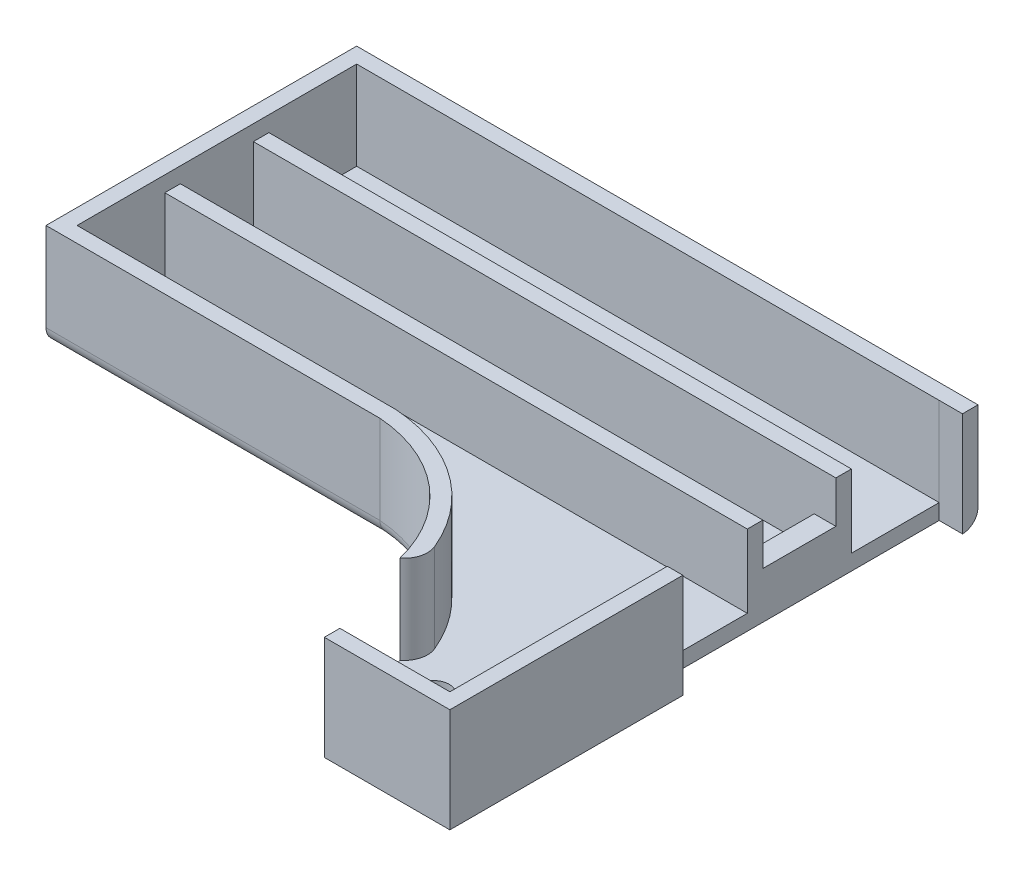
SolidWorks part; units mm, degrees
ref_plane "Alzado" through (0, 0, 0) normal (0, 0, 1) x (1, 0, 0)
ref_plane "Planta" through (0, 0, 0) normal (0, 1, 0) x (1, 0, 0)
ref_plane "Vista lateral" through (0, 0, 0) normal (1, 0, 0) x (0, 0, -1)
sketch "Croquis1" plane through (0, 0, 0) normal (0, 1, 0) x (1, 0, 0)
  line L0 (20, -10) -> (20, -24)
  line L1 (20, -24) -> (9, -24)
  line L2 (-20, -10) -> (-20, 10)
  line L3 (-20, 10) -> (20, 10)
  line L4 (20, -10) -> (20, 10)
  line L5 (-20, -10) -> (1.5, -10)
  arc A0 (9, -24) -> (1.5, -10) centre (0.7933, -19.3875) ccw
  point P0 (0, 0)
  point P10 (1.5, -10)
  dimension "D1" = 20
  dimension "D2" = 40
  dimension "D3" = 14
  dimension "D4" = 11
  dimension "D5" = 21.5
extrude "Saliente-Extruir2" add sketch "Croquis1" along normal blind 4 contours L4 L3 L2 L5 A0 L1 L0
shell "Vaciado1" thickness 1 removed face at (2.3903, 4, 7.657)
sketch "Croquis9" plane through (20, 0, 0) normal (1, 0, 0) x (0, 0, -1)
  line L0 (0, 4) -> (0, 0)
  line L1 (10, 4) -> (-24, 4) construction
  line L2 (-24, 0) -> (10, 0) construction
  line L3 (10, 4) -> (10, 0) construction
  line L5 (-9.0006, 0) -> (9.0006, 0)
  line L6 (-9.0006, 0) -> (-9.0006, 4)
  line L7 (-9.0006, 4) -> (9.0006, 4)
  line L8 (9.0006, 0) -> (9.0006, 4)
  line L9 (-9.0006, 0) -> (9.0006, 4) construction
  line L10 (-9.0006, 4) -> (9.0006, 0) construction
  point P8 (0, 2)
  line M2 (-24, 0) -> (10, 0)
  line M4 (10, 4) -> (-24, 4)
  dimension "D1" = 10
extrude "Cortar-Extruir2" cut sketch "Croquis9" against normal blind 1.5 contours L8 L0 M2 M4 | L6 L0 M2 M4 region at (20, 2, -4.5003) region at (20, 2, 4.5003)
sketch "Croquis12" plane through (0, 1, 0) normal (0, 1, 0) x (1, 0, 0)
  line L0 (18.5, -0.0003) -> (-19, 0) construction
  line L1 (18.5, -9.0006) -> (18.5, 9) construction
  line L2 (-19, -9) -> (-19, 9) construction
  line L3 (-0.25, -2.8502) -> (-0.25, 2.8498)
  line L5 (18.5, -2.3502) -> (-19, -2.3502)
  line L6 (18.5, -2.3502) -> (18.5, -3.3502)
  line L7 (18.5, -3.3502) -> (-19, -3.3502)
  line L8 (-19, -2.3502) -> (-19, -3.3502)
  line L9 (18.5, -2.3502) -> (-19, -3.3502) construction
  line L10 (18.5, -3.3502) -> (-19, -2.3502) construction
  line L11 (18.5, 2.3498) -> (-19, 2.3498)
  line L12 (18.5, 2.3498) -> (18.5, 3.3498)
  line L13 (18.5, 3.3498) -> (-19, 3.3498)
  line L14 (-19, 2.3498) -> (-19, 3.3498)
  line L15 (18.5, 2.3498) -> (-19, 3.3498) construction
  line L16 (18.5, 3.3498) -> (-19, 2.3498) construction
  point P9 (-0.25, -0.0002)
  dimension "D1" = 5.7
  dimension "D2" = 1
  dimension "D3" = 1
extrude "Saliente-Extruir6" add sketch "Croquis12" along normal blind 4.7 contours L7 L8 L5 L6 | L13 L14 L11 L12
sketch "Croquis14" plane through (0, 1, 0) normal (0, 1, 0) x (1, 0, 0)
  line L0 (18.5, 2.3498) -> (-19, 2.3498) construction
  line L1 (18.5, -2.3502) -> (17.1045, -2.3502)
  line L2 (18.5, -2.3502) -> (18.5, 2.3498)
  line L3 (18.5, 2.3498) -> (17.1045, 2.3498)
  line L4 (17.1045, -2.3502) -> (17.1045, 2.3498)
extrude "Saliente-Extruir7" add sketch "Croquis14" along normal blind 2
sketch "Croquis15" plane through (0, 1, 0) normal (0, 1, 0) x (1, 0, 0)
  line L0 (18.5, -3.3502) -> (-19, -3.3502) construction
  circle A0 centre (14.5685, -11.6502) radius 0.8
  dimension "D1" = 1.6
  dimension "D2" = 8.3
extrude "Saliente-Extruir8" add sketch "Croquis15" along normal blind 3.5
sketch "Croquis16" plane through (0, 4, 0) normal (0, 1, 0) x (1, 0, 0)
  line L0 (14.8572, -23) -> (14.8572, -17.9) construction
  line L1 (14.8572, -17.9) -> (12.8572, -17.9) construction
  line L2 (19, -23) -> (10.5607, -23) construction
  circle A0 centre (12.8572, -17.9) radius 0.8
  dimension "D3" = 1.6
  dimension "D1" = 5.1
  dimension "D2" = 2
extrude "Saliente-Extruir11" add sketch "Croquis16" along normal blind 1.78 and the other way up to vertex (3 mm away) other way up to point (18.5, 1, 9.0006)
sketch "Croquis59" plane through (0, 0, 24) normal (0, 0, 1) x (1, 0, 0)
  line L0 (20, 4) -> (9, 4) construction
  line L1 (11.919, 4) -> (8.1539, 4)
  line L2 (11.919, 4) -> (11.919, -0.1782)
  line L3 (11.919, -0.1782) -> (8.1539, -0.1782)
  line L4 (8.1539, 4) -> (8.1539, -0.1782)
extrude "Cortar-Extruir4" cut sketch "Croquis59" against normal blind 2.6
sketch "Croquis86" plane through (11.919, 0, 0) normal (-1, 0, 0) x (0, 0, 1)
  line L0 (24, 0) -> (24, 4) construction
  line L1 (23, 4) -> (24, 4)
  line L2 (23, 4) -> (23, 1)
  line L3 (23, 1) -> (24, 1)
  line L4 (24, 4) -> (24, 1)
sketch "Croquis88" plane through (0, 0, 21.4) normal (0, 0, 1) x (1, 0, 0)
  line L0 (9.9898, 4) -> (9.9898, 0) construction
  line L1 (11.0111, 4) -> (9.9898, 4)
  line L2 (11.0111, 4) -> (11.0111, 1)
  line L3 (11.0111, 1) -> (9.9898, 1)
  line L4 (9.9898, 4) -> (9.9898, 1)
extrude "Cortar-Extruir7" cut sketch "Croquis88" against normal blind 2.6
sketch "Croquis89" plane through (11.0111, 0, 0) normal (-1, 0, 0) x (0, 0, 1)
  line L4 (21.4, 1) -> (21.4, 4)
  line L5 (21.4, 4) -> (18.8, 4)
  line L6 (18.8, 4) -> (18.8, 1)
  line L7 (18.8, 1) -> (21.4, 1)
  line L8 (21.4, 1) -> (21.4, 4)
  line L9 (21.4, 4) -> (18.8, 4)
  line L10 (18.8, 4) -> (18.8, 1)
  line L11 (18.8, 1) -> (21.4, 1)
  dimension "D1" = 0
extrude "Cortar-Extruir8" cut sketch "Croquis89" against normal blind 1
sketch "Croquis90" plane through (0, 0, 18.8) normal (0, 0, 1) x (1, 0, 0)
  line L1 (11.1908, 4) -> (8.9429, 4)
  line L2 (11.1908, 4) -> (11.1908, 1)
  line L3 (11.1908, 1) -> (8.9429, 1)
  line L4 (8.9429, 4) -> (8.9429, 1)
extrude "Cortar-Extruir9" cut sketch "Croquis90" against normal blind 1.65
sketch "Croquis98" plane through (0, 1, 0) normal (0, 1, 0) x (1, 0, 0)
  line L0 (16.8, -19.13) -> (16.8, -23) construction
  line L1 (19, -23) -> (11.919, -23) construction
  line L2 (19, -23) -> (11.919, -23) construction
  line L3 (16.8, -20.7019) -> (17.8, -20.7019)
  line L4 (16.8, -20.7019) -> (16.8, -23)
  line L5 (16.8, -23) -> (17.8, -23)
  line L6 (17.8, -20.7019) -> (17.8, -23)
  line L8 (15.4, -19.13) -> (15.4, -23) construction
  line L9 (14, -23) -> (13, -23)
  line L10 (14, -20.7019) -> (14, -23)
  line L11 (14, -20.7019) -> (13, -20.7019)
  line L12 (13, -20.7019) -> (13, -23)
  line L13 (15.4, -19.13) -> (19, -19.13) construction
  line L14 (19, -23) -> (19, -9.0006) construction
  dimension "D1" = 3.6
  dimension "D2" = 2.8
  dimension "D3" = 1
extrude "Saliente-Extruir13" add sketch "Croquis98" along normal blind 4.8 separate body
fillet "Redondeo6" radius 1.5 1 edges at (10.9642, 2.5, 17.15)
sketch "Croquis99" plane through (0, 4.5, 0) normal (0, 1, 0) x (1, 0, 0)
  circle A1 centre (14.5685, -11.6502) radius 0.8
  circle A2 centre (14.5685, -11.6502) radius 0.8
  dimension "D1" = 0
extrude "Saliente-Extruir14" add sketch "Croquis99" along normal blind 1.25
sketch "Croquis100" plane through (0, 5.7, 0) normal (0, 1, 0) x (1, 0, 0)
  line L6 (11.919, -23) -> (11.919, -24)
  line L7 (11.919, -24) -> (20, -24)
  line L8 (20, -24) -> (20, -9.0006)
  line L9 (20, -9.0006) -> (19, -9.0006)
  line L10 (19, -9.0006) -> (19, -23)
  line L11 (19, -23) -> (11.919, -23)
  line L12 (1.5366, -9) -> (-19, -9)
  line L13 (-19, -9) -> (-19, -3.3502)
  line L14 (-19, -3.3502) -> (-19, -2.3502)
  line L15 (-19, -2.3502) -> (-19, 2.3498)
  line L16 (-19, 2.3498) -> (-19, 3.3498)
  line L17 (-19, 3.3498) -> (-19, 9)
  line L18 (-19, 9) -> (18.5, 9)
  line L19 (18.5, 9) -> (18.5, 9.0006)
  line L20 (18.5, 9.0006) -> (20, 9.0006)
  line L21 (20, 10) -> (-20, 10)
  line L22 (-20, 10) -> (-20, -10)
  line L23 (-20, -10) -> (1.5, -10)
  line L24 (1.5366, -9) -> (-19, -9)
  line L25 (-19, -9) -> (-19, -3.3502)
  line L26 (-19, -3.3502) -> (-19, -2.3502)
  line L27 (-19, -2.3502) -> (-19, 2.3498)
  line L28 (-19, 2.3498) -> (-19, 3.3498)
  line L29 (-19, 3.3498) -> (-19, 9)
  line L30 (-19, 9) -> (18.5, 9)
  line L31 (18.5, 9) -> (18.5, 9.0006)
  line L32 (18.5, 9.0006) -> (20, 9.0006)
  line L33 (20, 10) -> (-20, 10)
  line L34 (-20, 10) -> (-20, -10)
  line L35 (-20, -10) -> (1.5, -10)
  line L36 (11.919, -23) -> (11.919, -24)
  line L37 (11.919, -24) -> (20, -24)
  line L38 (20, -24) -> (20, -9.0006)
  line L39 (20, -9.0006) -> (19, -9.0006)
  line L40 (19, -9.0006) -> (19, -23)
  line L41 (19, -23) -> (11.919, -23)
  line L49 (20, 9.0006) -> (20, 10)
  line L50 (20, 9.0006) -> (20, 10)
  arc A6 (9.9376, -17.15) -> (1.5, -10) centre (0.7933, -19.3875) ccw
  arc A7 (9.9376, -17.15) -> (10.4074, -15.3848) centre (9.0227, -15.9614) ccw
  arc A8 (10.4074, -15.3848) -> (1.5366, -9) centre (0.7933, -19.3875) ccw
  arc A12 (9.9376, -17.15) -> (1.5, -10) centre (0.7933, -19.3875) ccw
  arc A13 (9.9376, -17.15) -> (10.4074, -15.3848) centre (9.0227, -15.9614) ccw
  arc A14 (10.4074, -15.3848) -> (1.5366, -9) centre (0.7933, -19.3875) ccw
  dimension "D1" = 0
  dimension "D2" = 0
extrude "Saliente-Extruir15" add sketch "Croquis100" against normal up to surface (1.7 mm away) and the other way blind 1 up to face at (16.973, 4, 18.6669)
sketch "Croquis101" plane through (0, 5.78, 0) normal (0, 1, 0) x (1, 0, 0)
  circle A2 centre (14.5685, -11.6502) radius 1
  circle A3 centre (12.8572, -17.9) radius 1
  dimension "D1" = 2
  dimension "D2" = 2
extrude "Cortar-Extruir10" cut sketch "Croquis101" against normal through all
sketch "Croquis102" plane through (0, 1, 0) normal (0, 1, 0) x (1, 0, 0)
  line L1 (13, -23) -> (17.8, -23)
  line L2 (13, -23) -> (13, -20.7019)
  line L3 (13, -20.7019) -> (17.8, -20.7019)
  line L4 (17.8, -23) -> (17.8, -20.7019)
extrude "Cortar-Extruir11" cut sketch "Croquis102" along normal through all
fillet "Fillet2" radius 1 2 edges at (-9.25, 0, 10) (8.3437, 0, 13.7646)
fillet "Fillet3" radius 1 1 edges at (0, 0, -10)
